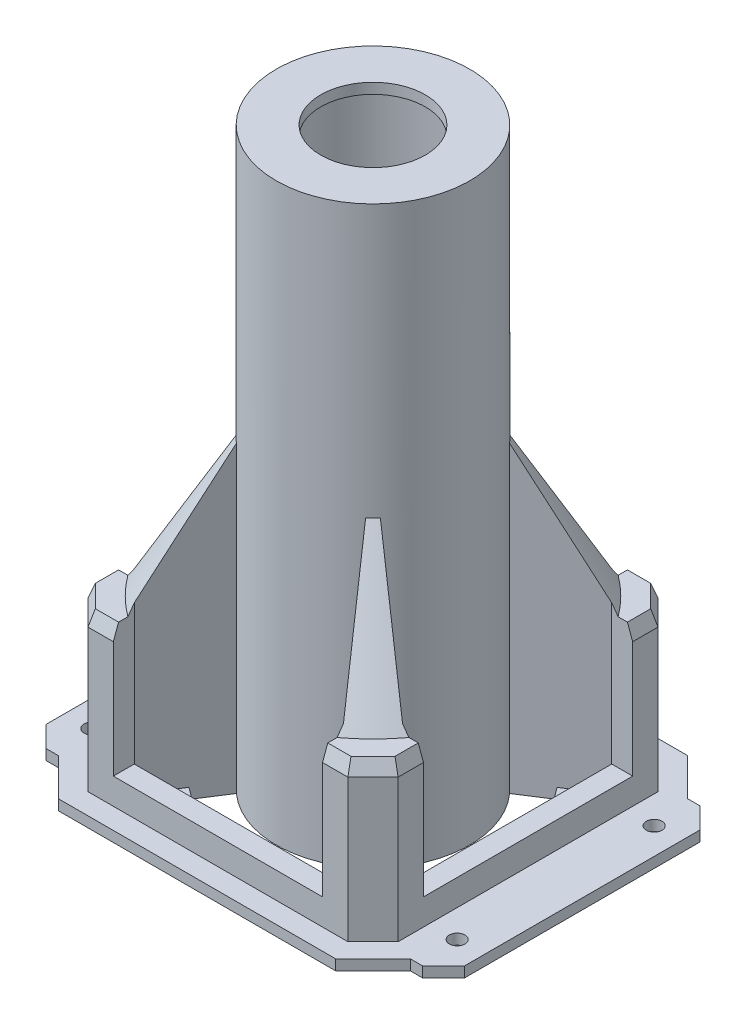
SolidWorks part; units mm, degrees
ref_plane "Front Plane" through (0, 0, 0) normal (0, 0, 1) x (1, 0, 0)
ref_plane "Top Plane" through (0, 0, 0) normal (0, 1, 0) x (1, 0, 0)
ref_plane "Right Plane" through (0, 0, 0) normal (1, 0, 0) x (0, 0, -1)
sketch "Sketch3" plane through (0, 0, 0) normal (0, 0, 1) x (1, 0, 0)
  line L16 (-999.7738, 0) -> (49000.2262, 0) construction
  line L17 (0, -1000) -> (0, 49000) construction
  line L21 (-25.65, 0) -> (-25.65, 30)
  line L22 (-25.65, 30) -> (-29.65, 30)
  line L23 (-29.65, 30) -> (-29.65, 0)
  line L33 (-29.65, 0) -> (-25.65, 0)
  dimension "D1" = 30
  dimension "D5" = 29.65
  dimension "D7" = 4
sketch "Sketch7" plane through (0, 0, 0) normal (0, 1, 0) x (1, 0, 0)
  line L0 (-30, -30) -> (30, -30) construction
  line L5 (30, -30) -> (-30, 30) construction
  line L6 (30, 30) -> (-30, -30) construction
  line L7 (30, -30) -> (30, 30) construction
  line L8 (30, 30) -> (-30, 30) construction
  line L9 (-30, 30) -> (-30, -30) construction
  line L10 (-30, 25) -> (-30, -25)
  line L11 (-30, -25) -> (-25, -30)
  line L12 (-25, -30) -> (25, -30)
  line L13 (25, -30) -> (30, -25)
  line L14 (30, -25) -> (30, 25)
  line L15 (30, 25) -> (25, 30)
  line L16 (25, 30) -> (-25, 30)
  line L17 (-25, 30) -> (-30, 25)
  point P0 (0, 0)
  dimension "D1" = 60
  dimension "D2" = 60
  dimension "D3" = 45
  dimension "D4" = 50
sweep "Sweep4" add profiles "Sketch3" path "Sketch7"
chamfer "Chamfer1" distance 1 angle 70 9 edges at (27.2525, 30, -27.2525) (0, 30, -29.65) (-27.2525, 30, -27.2525) (-29.65, 30, -12.4275) (-29.65, 30, 12.4275) (-27.2525, 30, 27.2525) (29.65, 30, 0) (27.2525, 30, 27.2525) (0, 30, 29.65)
sketch "Sketch13" plane through (0, 0, 0) normal (0, -1, 0) x (1, 0, 0)
  line L8 (-33.65, 26.5119) -> (-33.65, -26.5119)
  line L9 (-26.5119, 33.65) -> (26.5119, 33.65)
  line L10 (26.5119, 33.65) -> (33.65, 26.5119)
  line L11 (33.65, 26.5119) -> (33.65, -26.5119)
  line L12 (33.65, -26.5119) -> (26.5119, -33.65)
  line L13 (26.5119, -33.65) -> (-26.5119, -33.65)
  line L14 (-26.5119, -33.65) -> (-33.65, -26.5119)
  line L15 (-33.65, 26.5119) -> (-26.5119, 33.65)
  line L16 (-29.65, 24.855) -> (-29.65, 0) construction
  line L17 (24.855, 29.65) -> (-24.855, 29.65) construction
  line L18 (29.65, -24.855) -> (29.65, 24.855) construction
  line L19 (-24.855, -29.65) -> (24.855, -29.65) construction
  line L20 (-29.65, -24.855) -> (-24.855, -29.65) construction
  line L21 (24.855, -29.65) -> (29.65, -24.855) construction
  line L22 (29.65, 24.855) -> (24.855, 29.65) construction
  line L24 (-24.855, 29.65) -> (-29.65, 24.855) construction
  circle A0 centre (0, 0) radius 25
  dimension "D1" = 50
  dimension "D2" = 4
  dimension "D3" = 4
  dimension "D4" = 4
  dimension "D5" = 4
  dimension "D6" = 4
  dimension "D7" = 4
  dimension "D8" = 4
  dimension "D9" = 4
extrude "Boss-Extrude1" add sketch "Sketch13" along normal blind 2
ref_plane "Plane1" through (0, 5, 0) normal (0, 1, 0) x (1, 0, 0)
sketch "Sketch15" plane through (0, 5, 0) normal (0, 1, 0) x (1, 0, 0)
  line L1 (50, -20) -> (-50, -20)
  line L2 (50, -20) -> (50, 20)
  line L3 (50, 20) -> (-50, 20)
  line L4 (-50, -20) -> (-50, 20)
  line L5 (50, -20) -> (-50, 20) construction
  line L6 (50, 20) -> (-50, -20) construction
  point P0 (0, 0)
  dimension "D1" = 40
  dimension "D2" = 100
extrude "Cut-Extrude8" cut sketch "Sketch15" along normal through all
sketch "Sketch16" plane through (0, 5, 0) normal (0, 1, 0) x (1, 0, 0)
  line L1 (-20, -50) -> (20, -50)
  line L2 (-20, -50) -> (-20, 50)
  line L3 (-20, 50) -> (20, 50)
  line L4 (20, -50) -> (20, 50)
  line L5 (-20, -50) -> (20, 50) construction
  line L6 (-20, 50) -> (20, -50) construction
  point P0 (0, 0)
  dimension "D1" = 40
  dimension "D2" = 100
extrude "Cut-Extrude9" cut sketch "Sketch16" along normal through all
sketch "Sketch17" plane through (0, -2, 0) normal (0, -1, 0) x (1, 0, 0)
  line L1 (-34.925, -18.8341) -> (34.925, -18.8341) construction
  line L2 (-34.925, -18.8341) -> (-34.925, 18.8341) construction
  line L3 (-34.925, 18.8341) -> (34.925, 18.8341) construction
  line L4 (34.925, -18.8341) -> (34.925, 18.8341) construction
  line L5 (-34.925, -18.8341) -> (34.925, 18.8341) construction
  line L6 (-34.925, 18.8341) -> (34.925, -18.8341) construction
  circle A0 centre (-34.925, 18.8341) radius 1.5
  circle A1 centre (34.925, 18.8341) radius 1.5
  circle A2 centre (34.925, -18.8341) radius 1.5
  circle A3 centre (-34.925, -18.8341) radius 1.5
  point P0 (0, 0)
  dimension "D1" = 3
  dimension "D2" = 69.85
  dimension "D3" = 37.6682
sketch "Sketch18" plane through (0, -2, 0) normal (0, -1, 0) x (1, 0, 0)
  line L1 (40, -26.5119) -> (-40, -26.5119)
  line L2 (40, -26.5119) -> (40, 26.5119)
  line L3 (40, 26.5119) -> (-40, 26.5119)
  line L4 (-40, -26.5119) -> (-40, 26.5119)
  line L5 (40, -26.5119) -> (-40, 26.5119) construction
  line L6 (40, 26.5119) -> (-40, -26.5119) construction
  circle A0 centre (0, 0) radius 25
  circle A1 centre (0, 0) radius 25 construction
  point P0 (0, 0)
  dimension "D1" = 80
extrude "Boss-Extrude2" add sketch "Sketch18" against normal up to surface (2 mm away) up to face at (0, 0, 0)
extrude "Cut-Extrude10" cut sketch "Sketch17" against normal through all
chamfer "Chamfer2" distance 4 angle 45 4 edges at (40, -1, -26.5119) (-40, -1, -26.5119) (-40, -1, 26.5119) (40, -1, 26.5119)
sketch "Sketch19" plane through (0, -2, 0) normal (0, 1, 0) x (1, 0, 0)
  line L0 (-1000, 0) -> (49000, 0) construction
  circle A1 centre (0, 0) radius 18.5
  circle A2 centre (0, 0) radius 16.5
  dimension "D1" = 2
  dimension "D2" = 33
extrude "Boss-Extrude3" add sketch "Sketch19" along normal blind 108
sketch "Sketch27" plane through (0, -2, 0) normal (0, 1, 0) x (1, 0, 0)
  line L0 (-25.65, 20) -> (-13.7695, 12.3552)
  line L1 (-20, 25.65) -> (-12.3552, 13.7695)
  line L2 (-25.65, 20) -> (-25.65, 23.1982)
  line L3 (-25.65, 23.1982) -> (-23.1982, 25.65)
  line L4 (-23.1982, 25.65) -> (-20, 25.65)
  line L5 (0, 0) -> (-35355.3391, 35355.3391) construction
  line L6 (12.3552, 13.7695) -> (20, 25.65)
  line L7 (20, 25.65) -> (23.1982, 25.65)
  line L8 (23.1982, 25.65) -> (25.65, 23.1982)
  line L9 (25.65, 23.1982) -> (25.65, 20)
  line L10 (25.65, 20) -> (13.7695, 12.3552)
  line L11 (-13.7695, -12.3552) -> (-25.65, -20)
  line L12 (-25.65, -20) -> (-25.65, -23.1982)
  line L13 (-25.65, -23.1982) -> (-23.1982, -25.65)
  line L14 (-23.1982, -25.65) -> (-20, -25.65)
  line L15 (-20, -25.65) -> (-12.3552, -13.7695)
  line L16 (12.3552, -13.7695) -> (20, -25.65)
  line L17 (20, -25.65) -> (23.1982, -25.65)
  line L18 (23.1982, -25.65) -> (25.65, -23.1982)
  line L19 (25.65, -23.1982) -> (25.65, -20)
  line L20 (25.65, -20) -> (13.7695, -12.3552)
  line L21 (0, 0) -> (35355.3391, 35355.3391) construction
  circle A0 centre (0, 0) radius 18.5 construction
  arc A1 (-13.7695, 12.3552) -> (-12.3552, 13.7695) centre (0, 0) cw
  arc A2 (-13.7695, -12.3552) -> (-12.3552, -13.7695) centre (0, 0) ccw
  arc A3 (12.3552, -13.7695) -> (13.7695, -12.3552) centre (0, 0) ccw
  arc A4 (13.7695, 12.3552) -> (12.3552, 13.7695) centre (0, 0) ccw
  dimension "D1" = 2
  dimension "D2" = 2
  dimension "D3" = 2
  dimension "D4" = 2
extrude "Boss-Extrude5" add sketch "Sketch27" along normal up to surface (32 mm away) up to face at (-27.15, 30, -21.9097)
chamfer "Chamfer4" distance 15 angle 60 3 edges at (-13.0815, 30, 13.0815) (-13.0815, 30, -13.0815) (13.0815, 30, 13.0815)
sketch "Sketch28" plane through (0, 106, 0) normal (0, 1, 0) x (1, 0, 0)
  circle A2 centre (0, 0) radius 18.5
  circle A3 centre (0, 0) radius 18.5 construction
extrude "Boss-Extrude6" add sketch "Sketch28" along normal blind 2
sketch "Sketch29" plane through (0, 108, 0) normal (0, 1, 0) x (1, 0, 0)
  circle A0 centre (0, 0) radius 10
  dimension "D1" = 20
extrude "Cut-Extrude13" cut sketch "Sketch29" against normal blind 2
